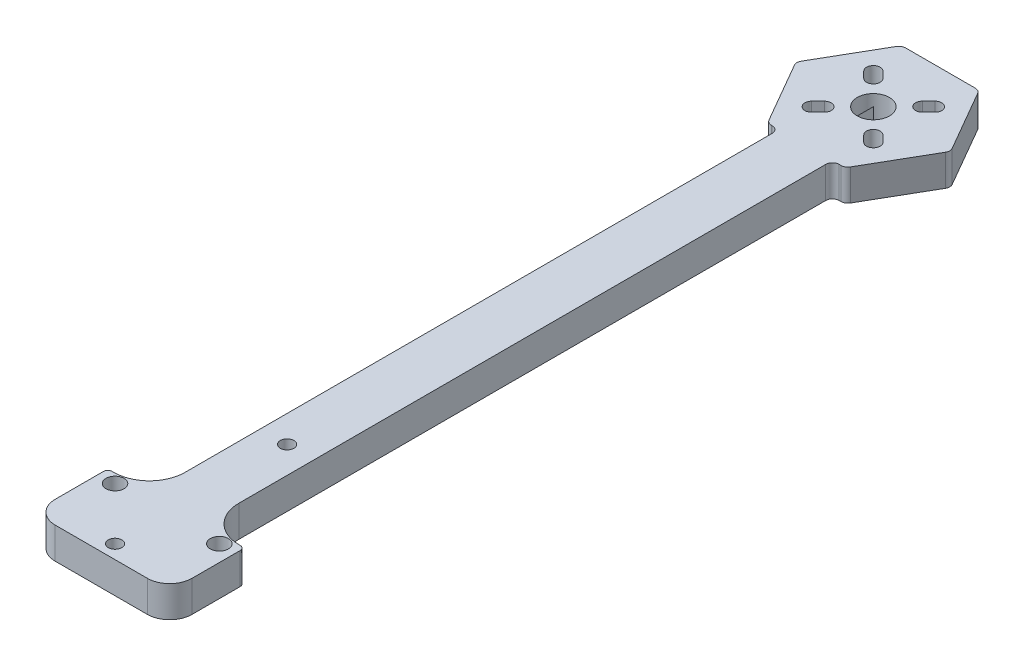
SolidWorks part; units mm, degrees
material "Thornel Mat VMA"
ref_plane "前视基准面" through (0, 0, 0) normal (0, 0, 1) x (1, 0, 0)
ref_plane "上视基准面" through (0, 0, 0) normal (0, 1, 0) x (1, 0, 0)
ref_plane "右视基准面" through (0, 0, 0) normal (1, 0, 0) x (0, 0, -1)
other "Configuration Table"
sketch "草图1" plane through (0, 0, 0) normal (0, 1, 0) x (1, 0, 0)
  line L0 (12, 0) -> (12, -0.0024)
  line L1 (0, 0) -> (12, 0)
  line L2 (0, 0) -> (0, 140.81)
  line L3 (0, 140.81) -> (12, 140.81)
  line L4 (12, 0) -> (12, 140.81)
  line L5 (-9.3063, -0.0024) -> (21.3085, -0.0024)
  line L6 (-9.3063, -0.0024) -> (-9.3063, -16.7665)
  line L7 (-9.3063, -16.7665) -> (21.3085, -16.7665)
  line L8 (21.3085, -0.0024) -> (21.3085, -16.7665)
  line L9 (-18.063, 181.9962) -> (30.3554, 181.9962)
  line L10 (-18.063, 181.9962) -> (-18.063, 140.81)
  line L11 (-18.063, 140.81) -> (30.3554, 140.81)
  line L12 (30.3554, 181.9962) -> (30.3554, 140.81)
  line L13 (12, -0.0024) -> (12, 0)
  line L14 (0, 0) -> (0, -0.0024)
  line L15 (0, -0.0024) -> (12, -0.0024)
  circle A3 centre (6, 24.8103) radius 1.52
  dimension "D1" = 140.81
  dimension "D2" = 12
extrude "凸台-拉伸1" add sketch "草图1" along normal blind 7 contours L8 L5 L1 L6 L7 | L1 L4 L3 L2 | L12 L9 L10 L11 L3 | L1 L14 L5 L0 region at (6, 0, 0.0012) region at (6, 0, -70.6017) region at (6.0011, 0, 8.3845) region at (6.1462, 0, -161.4031)
sketch "草图2" plane through (0, 7, 0) normal (0, 1, 0) x (1, 0, 0)
  line L0 (6.1462, 155.81) -> (6.1462, 140.81)
  line L1 (-18.063, 140.81) -> (30.3554, 140.81)
  line L2 (-18.063, 140.81) -> (-18.063, 181.9962)
  line L3 (-18.063, 181.9962) -> (30.3554, 181.9962)
  line L4 (30.3554, 140.81) -> (30.3554, 181.9962)
  line L5 (14.8064, 140.81) -> (23.4667, 155.81)
  line L6 (23.4667, 155.81) -> (14.8064, 170.81)
  line L7 (14.8064, 170.81) -> (-2.5141, 170.81)
  line L8 (-2.5141, 170.81) -> (-11.1743, 155.81)
  line L9 (-11.1743, 155.81) -> (-2.5141, 140.81)
  line L10 (-2.5141, 140.81) -> (14.8064, 140.81)
  line L11 (6.1462, 155.81) -> (17.1269, 144.8292)
  line L12 (13.0405, 148.9157) -> (14.1153, 149.9905)
  line L13 (14.1153, 149.9905) -> (12.7011, 151.4047)
  line L14 (12.7011, 151.4047) -> (11.6263, 150.3299)
  line L15 (11.9657, 147.8409) -> (10.5515, 149.2551)
  line L16 (11.9657, 163.7791) -> (10.5515, 162.3649)
  line L17 (14.1153, 161.6295) -> (12.7011, 160.2153)
  line L18 (-1.8229, 161.6295) -> (-0.4087, 160.2153)
  line L19 (6.1462, 155.81) -> (23.4667, 155.81)
  line L20 (0.3267, 163.7791) -> (1.7409, 162.3649)
  line L21 (-1.8229, 149.9905) -> (-0.4087, 151.4047)
  line L22 (0.3267, 147.8409) -> (1.7409, 149.2551)
  line L23 (6.1462, 155.81) -> (6, 24.8103)
  circle A0 centre (6.1462, 155.81) radius 15 construction
  circle A1 centre (6.1462, 155.81) radius 3.6
  circle A4 centre (11.6263, 150.3299) radius 1.52
  circle A5 centre (13.0405, 148.9157) radius 1.52
  circle A6 centre (11.6263, 161.2901) radius 1.52
  circle A7 centre (13.0405, 162.7043) radius 1.52
  circle A8 centre (-0.7481, 162.7043) radius 1.52
  circle A9 centre (0.6661, 161.2901) radius 1.52
  circle A10 centre (-0.7481, 148.9157) radius 1.52
  circle A11 centre (0.6661, 150.3299) radius 1.52
  line M16 (30.3554, 140.81) -> (30.3554, 181.9962)
  line M17 (30.3554, 181.9962) -> (-18.063, 181.9962)
  line M18 (-18.063, 181.9962) -> (-18.063, 140.81)
  line M19 (-18.063, 140.81) -> (0, 140.81)
  dimension "D2" = 45
  dimension "D3" = 7.75
  dimension "D8" = 130.9997
  dimension "D1" = 15
  dimension "D4" = 9.75
  dimension "D5" = 90
  dimension "D6" = 90
  dimension "D7" = 1.52
extrude "切除-拉伸2" cut sketch "草图2" against normal blind 10 contours L19 A1 L0 | L0 A1 L11 | L11 A1 L19 | A10 A11 | A11 A10 | A11 A10 | A10 A11 L21 | L22 A11 A10 | A5 A4 L15 | A5 L11 A4 | A5 A4 L14 L11 | A4 A5 L11 | L11 A5 A4 | L14 A4 L11 | A5 L13 A4 | L12 A5 A4 L11 | L11 A5 L12 | A6 A7 | A7 A6 | A7 A6 | A6 A7 L16 | L17 A7 A6 | A9 A8 | A8 A9 | A9 L20 A8 | A9 A8 | A9 A8 L18 | L9 L8 L7 L6 L5 L1 M16 M17 M18 M19 | A4 A5 L11 region at (7.0412, 7, -153.6492) region at (8.3069, 7, -154.915) region at (5.6368, 7, -156.32) region at (11.6263, 7, -151.2422) region at (10.9194, 7, -150.0395) region at (19.6871, 7, -163.6278) region at (12.4495, 7, -150.6598) region at (13.3306, 7, -150.62) region at (11.3361, 7, -148.6256) region at (12.6453, 7, -149.9347) region at (12.0215, 7, -149.3109) region at (13.9528, 7, -148.9157) region at (13.3703, 7, -149.739) region at (12.75, 7, -148.2089) region at (11.3361, 7, -162.9944) region at (13.2487, 7, -162.9125) region at (11.4181, 7, -161.0819) region at (12.3334, 7, -161.9972) region at (13.3306, 7, -161) region at (-1.0382, 7, -161) region at (-0.9563, 7, -162.9125) region at (0.8743, 7, -161.0819) region at (0.9562, 7, -162.9944) region at (-0.041, 7, -161.9972) region at (-0.9563, 7, -148.7075) region at (-1.0382, 7, -150.62) region at (0.8743, 7, -150.5381) region at (0.9562, 7, -148.6256) region at (-0.041, 7, -149.6228)
fillet "圆角1" radius 8 2 edges at (12, 3.5, 0.0024) (0, 3.5, 0.0024)
fillet "圆角3" radius 1 2 edges at (21.3085, 3.5, 0.0024) (-9.3063, 3.5, 0.0024)
fillet "圆角4" radius 5 2 edges at (-9.3063, 3.5, 16.7665) (21.3085, 3.5, 16.7665)
fillet "圆角5" radius 1.5 8 edges at (14.8064, 3.5, -170.81) (23.4667, 3.5, -155.81) (14.8064, 3.5, -140.81) (12, 3.5, -140.81) (0, 3.5, -140.81) (-2.5141, 3.5, -170.81) (-11.1743, 3.5, -155.81) (-2.5141, 3.5, -140.81)
sketch "草图3" plane through (0, 0, 0) normal (0, -1, 0) x (-1, 0, 0)
  circle A0 centre (-17.6673, -2.0224) radius 2.02
  circle A1 centre (5.6673, -2.0224) radius 2.02
  circle A2 centre (-6, -13.6897) radius 1.52
extrude "切除-拉伸3" cut sketch "草图3" against normal blind 10
